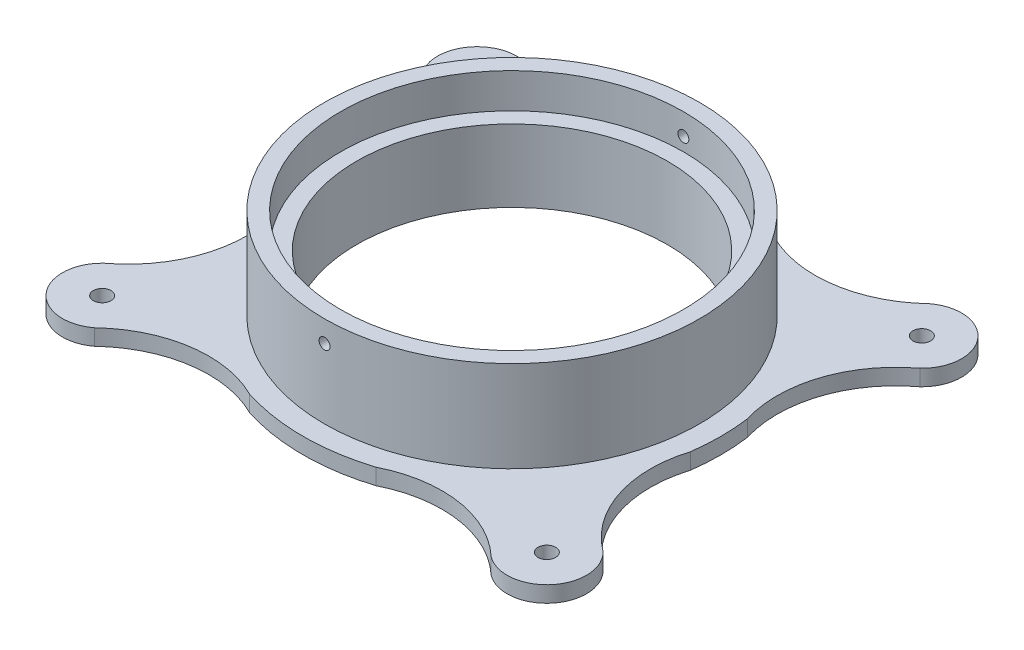
SolidWorks part; units mm, degrees
ref_plane "前视基准面" through (0, 0, 0) normal (0, 0, 1) x (1, 0, 0)
ref_plane "上视基准面" through (0, 0, 0) normal (0, 1, 0) x (1, 0, 0)
ref_plane "右视基准面" through (0, 0, 0) normal (1, 0, 0) x (0, 0, -1)
sketch "草图1" plane through (0, 0, 0) normal (0, 1, 0) x (1, 0, 0)
  line L0 (-64.683, 0) -> (63.4787, 0) construction
  line L1 (0, 51.7) -> (0, -47.2719) construction
  line L3 (41.5, -35) -> (-41.5, -35) construction
  line L4 (41.5, -35) -> (41.5, 35) construction
  line L5 (41.5, 35) -> (-41.5, 35) construction
  line L6 (-41.5, -35) -> (-41.5, 35) construction
  line L7 (41.5, -35) -> (-41.5, 35) construction
  line L8 (41.5, 35) -> (-41.5, -35) construction
  circle A0 centre (0, 0) radius 27.5 construction
  arc A2 (37.0224, 40.9121) -> (46.5719, 29.5891) centre (41.5, 35) cw
  arc A3 (-37.0224, -40.9121) -> (-46.5719, -29.5891) centre (-41.5, -35) cw
  arc A4 (37.0224, -40.9121) -> (46.5719, -29.5891) centre (41.5, -35) ccw
  arc A5 (-38.6311, 5.3518) -> (-38.6311, -5.3518) centre (0, 0) ccw
  arc A8 (-37.0224, 40.9121) -> (-46.5719, 29.5891) centre (-41.5, 35) ccw
  arc A15 (-11.7928, -37.1743) -> (11.7928, -37.1743) centre (0, 0) ccw
  arc A16 (38.6311, -5.3518) -> (38.6311, 5.3518) centre (0, 0) ccw
  arc A17 (11.7928, 37.1743) -> (-11.7928, 37.1743) centre (0, 0) ccw
  arc A18 (-11.7928, 37.1743) -> (-37.0224, 40.9121) centre (-21.7506, 56.9775) cw
  arc A19 (-38.6311, 5.3518) -> (-46.5719, 29.5891) centre (-59.8304, 11.8258) ccw
  arc A20 (-38.6311, -5.3518) -> (-46.5719, -29.5891) centre (-59.8304, -11.8258) cw
  arc A21 (-11.7928, -37.1743) -> (-37.0224, -40.9121) centre (-21.7506, -56.9775) ccw
  arc A22 (11.7928, -37.1743) -> (37.0224, -40.9121) centre (21.7506, -56.9775) cw
  arc A23 (38.6311, -5.3518) -> (46.5719, -29.5891) centre (59.8304, -11.8258) ccw
  arc A24 (38.6311, 5.3518) -> (46.5719, 29.5891) centre (59.8304, 11.8258) cw
  arc A25 (11.7928, 37.1743) -> (37.0224, 40.9121) centre (21.7506, 56.9775) ccw
  dimension "D1" = 70
  dimension "D2" = 55
  dimension "D3" = 83
  dimension "D4" = 78
extrude "凸台-拉伸2" add sketch "草图1" along normal blind 3
ref_plane "基准面1" through (0, 3, 0) normal (0, 1, 0) x (1, 0, 0)
sketch "草图2" plane through (0, 3, 0) normal (0, 1, 0) x (1, 0, 0)
  circle A0 centre (0, 0) radius 35
  dimension "D1" = 70
extrude "凸台-拉伸3" add sketch "草图2" along normal blind 17
ref_plane "基准面2" through (0, 20, 0) normal (0, 1, 0) x (1, 0, 0)
sketch "草图3" plane through (0, 20, 0) normal (0, 1, 0) x (1, 0, 0)
  circle A0 centre (0, 0) radius 25
  dimension "D1" = 50
ref_plane "基准面3" through (0, 0, 0) normal (1, 0, 0) x (0, 0, -1)
ref_plane "基准面4" through (0, 0, 0) normal (0, 0, 1) x (1, 0, 0)
hole_wizard "M2.5 螺纹孔1" positions "草图9" profile "草图10" tap size "M2.5" standard "GB" end condition through all
sketch "草图9" plane through (0, 0, 0) normal (0, 0, 1) x (1, 0, 0)
  line L1 (25, 20) -> (-25, 20) construction
  point P0 (0, 16)
  dimension "D1" = 4
sketch "草图10" plane through (0, 16, 0) normal (1, 0, 0) x (0, 1, 0)
  line L0 (0, 0) -> (0, 42.4163)
  line L1 (0, 42.4163) -> (1.025, 42.4163)
  line L2 (1.025, 42.4163) -> (1.025, 0)
  line L5 (1.025, 0) -> (0, 0)
  line L11 (0, -6.35) -> (0, 107.95) construction
  dimension "通孔螺纹孔钻头直径" = 2.05
  dimension "通孔螺纹孔钻头深度" = 42.4163
cosmetic thread "孔螺蚊线26" parameters "D2"=2.5
mirror "镜向3" about plane through (0, 0, 0) normal (0, 0, 1) of "M2.5 螺纹孔1"
ref_plane "基准面5" through (0, 0, 0) normal (0, -1, 0) x (-1, 0, 0)
sketch "草图21" plane through (0, 0, 0) normal (0, -1, 0) x (-1, 0, 0)
  line L1 (-41.5, 35) -> (41.5, 35) construction
  line L2 (-41.5, 35) -> (-41.5, -35) construction
  line L3 (-41.5, -35) -> (41.5, -35) construction
  line L4 (41.5, 35) -> (41.5, -35) construction
  circle A0 centre (-41.5, 35) radius 3
  circle A1 centre (41.5, 35) radius 3
  circle A2 centre (-41.5, -35) radius 3
  circle A3 centre (41.5, -35) radius 3
hole_wizard "M4 螺纹孔2" positions "草图24" profile "草图25" tap size "M4" standard "GB" end condition through all
sketch "草图24" plane through (0, 20, 0) normal (0, 1, 0) x (1, 0, 0)
  point P0 (-41.5, 35)
  point P3 (-41.5, -35)
  point P6 (41.5, -35)
  point P9 (41.5, 35)
sketch "草图25" plane through (-41.5, 20, -35) normal (1, 0, 0) x (0, 0, 1)
  line L0 (0, 0) -> (0, 20)
  line L1 (0, 20) -> (1.65, 20)
  line L2 (1.65, 20) -> (1.65, 0)
  line L5 (1.65, 0) -> (0, 0)
  line L11 (0, -6.35) -> (0, 107.95) construction
  dimension "通孔螺纹孔钻头直径" = 3.3
  dimension "通孔螺纹孔钻头深度" = 20
cosmetic thread "孔螺蚊线14" parameters "D2"=4
cosmetic thread "孔螺蚊线15" parameters "D2"=4
cosmetic thread "孔螺蚊线16" parameters "D2"=4
cosmetic thread "孔螺蚊线17" parameters "D2"=4
ref_plane "基准面6" through (0, 20, 0) normal (0, 1, 0) x (1, 0, 0)
ref_plane "基准面7" through (0, 20, 0) normal (0, 1, 0) x (1, 0, 0)
sketch "草图28" plane through (0, 20, 0) normal (0, 1, 0) x (1, 0, 0)
  circle A0 centre (0, 0) radius 32
  dimension "D1" = 64
extrude "切除-拉伸1" cut sketch "草图28" against normal blind 6.5
hole_wizard "M64 螺纹孔2" positions "草图29" profile "草图31" tap size "M64" standard "GB" end condition through all
sketch "草图29" plane through (0, 0, 0) normal (0, -1, 0) x (-1, 0, 0)
  point P0 (0, 0)
sketch "草图31" plane through (0, 0, 0) normal (1, 0, 0) x (0, 0, -1)
  line L0 (0, 0) -> (0, 20)
  line L1 (0, 20) -> (29, 20)
  line L2 (29, 20) -> (29, 0)
  line L5 (29, 0) -> (0, 0)
  line L11 (0, -6.35) -> (0, 107.95) construction
  dimension "通孔螺纹孔钻头直径" = 58
  dimension "通孔螺纹孔钻头深度" = 20
cosmetic thread "孔螺蚊线28" parameters "D2"=64
